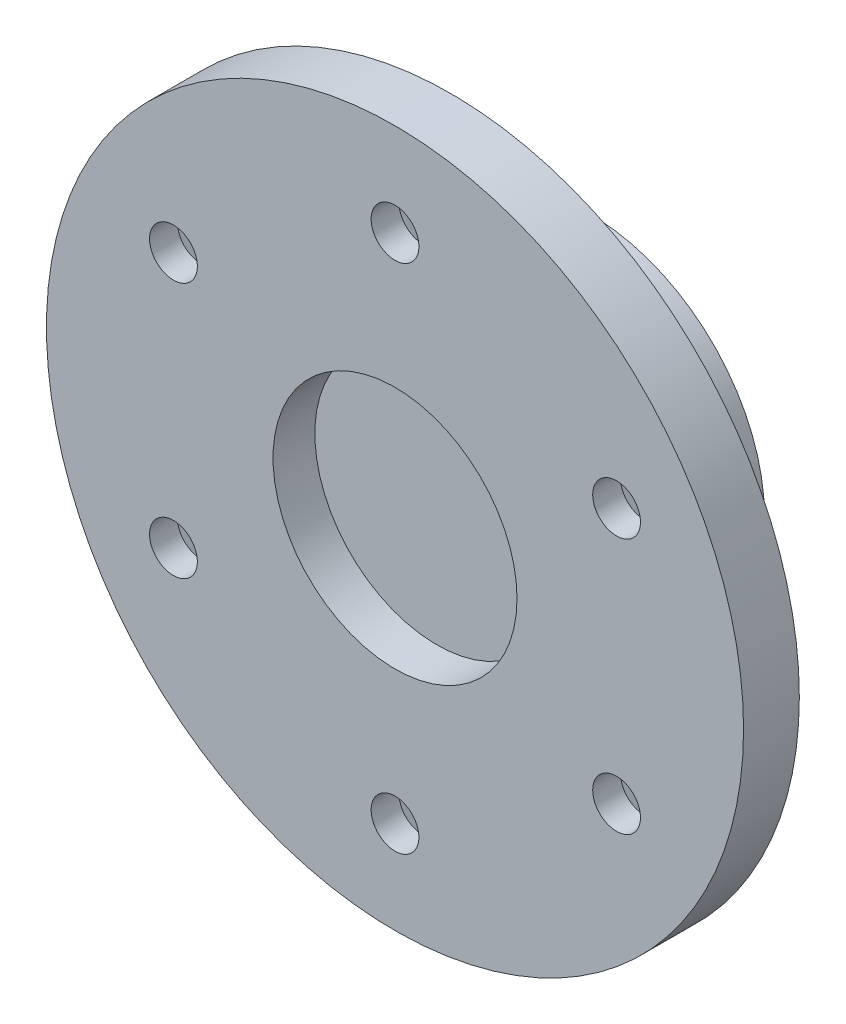
SolidWorks part; units mm, degrees
ref_plane "Front Plane" through (0, 0, 0) normal (0, 0, 1) x (1, 0, 0)
ref_plane "Top Plane" through (0, 0, 0) normal (0, 1, 0) x (1, 0, 0)
ref_plane "Right Plane" through (0, 0, 0) normal (1, 0, 0) x (0, 0, -1)
sketch "Sketch1" plane through (0, 0, 0) normal (0, 0, 1) x (1, 0, 0)
  circle A0 centre (0, 0) radius 25
  dimension "D1" = 50
extrude "Boss-Extrude1" add sketch "Sketch1" along normal blind 4
sketch "Sketch2" plane through (0, 0, 0) normal (0, 0, -1) x (-1, 0, 0)
  line L0 (0, 0) -> (0, 18.35) construction
  circle A0 centre (0, 18.35) radius 1.7136
  circle A1 centre (15.8916, 9.175) radius 1.7136
  circle A2 centre (15.8916, -9.175) radius 1.7136
  circle A3 centre (0, -18.35) radius 1.7136
  circle A4 centre (-15.8916, -9.175) radius 1.7136
  circle A5 centre (-15.8916, 9.175) radius 1.7136
  point P17 (0, 0)
  dimension "D1" = 18.35
  dimension "D2" = 6
extrude "Cut-Extrude1" cut sketch "Sketch2" against normal blind 4
sketch "Sketch3" plane through (0, 0, 0) normal (0, 0, -1) x (-1, 0, 0)
  line L0 (13.8708, 5.675) -> (17.9123, 5.675)
  line L1 (4.0415, 18.35) -> (2.0207, 21.85)
  line L2 (2.0207, 21.85) -> (-2.0207, 21.85)
  line L3 (-2.0207, 21.85) -> (-4.0415, 18.35)
  line L4 (-4.0415, 18.35) -> (-2.0207, 14.85)
  line L5 (-2.0207, 14.85) -> (2.0207, 14.85)
  line L6 (2.0207, 14.85) -> (4.0415, 18.35)
  line L7 (17.9123, 5.675) -> (19.933, 9.175)
  line L8 (19.933, 9.175) -> (17.9123, 12.675)
  line L9 (17.9123, 12.675) -> (13.8708, 12.675)
  line L10 (13.8708, 12.675) -> (11.8501, 9.175)
  line L11 (11.8501, 9.175) -> (13.8708, 5.675)
  line L12 (11.8501, -9.175) -> (13.8708, -12.675)
  line L13 (13.8708, -12.675) -> (17.9123, -12.675)
  line L14 (17.9123, -12.675) -> (19.933, -9.175)
  line L15 (19.933, -9.175) -> (17.9123, -5.675)
  line L16 (17.9123, -5.675) -> (13.8708, -5.675)
  line L17 (13.8708, -5.675) -> (11.8501, -9.175)
  line L18 (-2.0207, -14.85) -> (-4.0415, -18.35)
  line L19 (-4.0415, -18.35) -> (-2.0207, -21.85)
  line L20 (-2.0207, -21.85) -> (2.0207, -21.85)
  line L21 (2.0207, -21.85) -> (4.0415, -18.35)
  line L22 (4.0415, -18.35) -> (2.0207, -14.85)
  line L23 (2.0207, -14.85) -> (-2.0207, -14.85)
  line L24 (-13.8708, -5.675) -> (-17.9123, -5.675)
  line L25 (-17.9123, -5.675) -> (-19.933, -9.175)
  line L26 (-19.933, -9.175) -> (-17.9123, -12.675)
  line L27 (-17.9123, -12.675) -> (-13.8708, -12.675)
  line L28 (-13.8708, -12.675) -> (-11.8501, -9.175)
  line L29 (-11.8501, -9.175) -> (-13.8708, -5.675)
  line L30 (-11.8501, 9.175) -> (-13.8708, 12.675)
  line L31 (-13.8708, 12.675) -> (-17.9123, 12.675)
  line L32 (-17.9123, 12.675) -> (-19.933, 9.175)
  line L33 (-19.933, 9.175) -> (-17.9123, 5.675)
  line L34 (-17.9123, 5.675) -> (-13.8708, 5.675)
  line L35 (-13.8708, 5.675) -> (-11.8501, 9.175)
  circle A0 centre (0, 18.35) radius 3.5 construction
  point P42 (0, 0)
  dimension "D1" = 7
  dimension "D2" = 6
extrude "Cut-Extrude2" cut sketch "Sketch3" against normal blind 2
sketch "Sketch4" plane through (0, 0, 0) normal (0, 0, -1) x (-1, 0, 0)
  line L0 (0, 0) -> (0, 1) construction
  circle A1 centre (0, 1) radius 3
  circle A2 centre (0, 0) radius 12.5
  dimension "D1" = 6
  dimension "D3" = 25
  dimension "D2" = 1
extrude "Boss-Extrude2" add sketch "Sketch4" along normal blind 10
ref_plane "Plane1" through (0, 12.5, 0) normal (0, 1, 0) x (1, 0, 0)
sketch "Sketch5" plane through (0, 12.5, 0) normal (0, 1, 0) x (1, 0, 0)
  circle A0 centre (0, 5) radius 1.6
  dimension "D1" = 3.2
  dimension "D2" = 5
  dimension "D3" = 12.5
extrude "Cut-Extrude3" cut sketch "Sketch5" against normal blind 12.5
sketch "Sketch6" plane through (0, 12.5, 0) normal (0, 1, 0) x (1, 0, 0)
  circle A0 centre (0, 5) radius 3.1
  dimension "D1" = 6.2
extrude "Cut-Extrude4" cut sketch "Sketch6" against normal blind 6
ref_plane "Plane2" through (0, 1.5, 0) normal (0, 1, 0) x (1, 0, 0)
sketch "Sketch7" plane through (0, 1.5, 0) normal (0, 1, 0) x (1, 0, 0)
  line L1 (2.1743, 7.9) -> (-12.5, 7.9)
  line L3 (2.1743, 2.1) -> (-12.5, 2.1)
  line L4 (-12.5, 7.9) -> (-12.5, 2.1)
  line L5 (3, 10) -> (-3, 10) construction
  line L15 (2.1743, 7.9) -> (3.8486, 5)
  line L16 (3.8486, 5) -> (2.1743, 2.1)
  dimension "D5" = 16.3486
  dimension "D1" = 14.6743
  dimension "D2" = 5.8
  dimension "D3" = 2.1
  dimension "D4" = 14.6743
fillet "Fillet1" radius 1.5 1 edges at (12.5, 0, 0) type face fillet first side face at (0.608, 12.4852, -8.0398) second side face at (12.5, 0, 0)
sketch "Sketch9" plane through (0, 0, 4) normal (0, 0, 1) x (1, 0, 0)
  circle A0 centre (0, 0) radius 8.75
  dimension "D1" = 17.5
extrude "Cut-Extrude6" cut sketch "Sketch9" against normal blind 3
sketch "Sketch12" plane through (0, 0, -10) normal (0, 0, -1) x (-1, 0, 0)
  line L6 (-2.75, 4.5) -> (2.75, 4.5)
  line L7 (-2.75, 4.5) -> (-2.75, 2)
  line L8 (-2.75, 2) -> (2.75, 2)
  line L9 (2.75, 4.5) -> (2.75, 2)
  point P1 (0, 2)
  dimension "D1" = 5.5
  dimension "D2" = 2
  dimension "D4" = 2.5
extrude "Cut-Extrude7" cut sketch "Sketch12" against normal blind 10
equation "\"mm\"=1.5"
